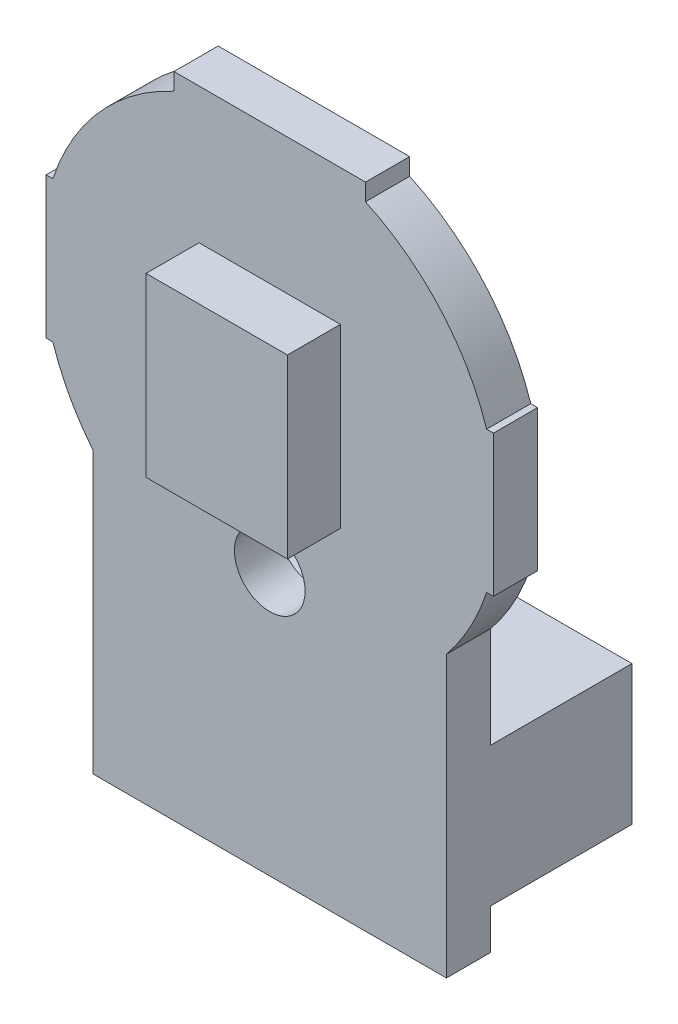
SolidWorks part; units mm, degrees
material "Acetal (Delrin)"
ref_plane "Front" through (0, 0, 0) normal (0, 0, 1) x (1, 0, 0)
ref_plane "Top" through (0, 0, 0) normal (0, 1, 0) x (1, 0, 0)
ref_plane "Right" through (0, 0, 0) normal (1, 0, 0) x (0, 0, -1)
sketch "Sketch1" plane through (0, 0, 0) normal (0, 0, 1) x (1, 0, 0)
  line L0 (-6.35, -9.4973) -> (6.35, -9.4973)
  line L1 (0, -9.4973) -> (0, 0) construction
  line L2 (0, 0) -> (0, 5.7658) construction
  line L3 (-6.35, -9.4973) -> (-6.35, 0.581)
  line L4 (6.35, -9.4973) -> (6.35, 0.581)
  line L7 (-8.0391, 5.7658) -> (0, 5.7658) construction
  line L8 (0, 5.7658) -> (8.0391, 5.7658) construction
  line L10 (3.4417, 13.8199) -> (-3.4417, 13.8199)
  line L11 (0, 1.27) -> (0, 13.8199) construction
  line L12 (3.4417, 13.8199) -> (3.4417, 13.2062)
  line L13 (-3.4417, 13.8199) -> (-3.4417, 13.2062)
  line L14 (-8.0391, 8.3058) -> (-8.0391, 3.2258)
  line L15 (8.0391, 8.3058) -> (8.0391, 3.2258)
  line L16 (-8.0391, 8.3058) -> (-7.7944, 8.3058)
  line L17 (8.0391, 8.3058) -> (7.7944, 8.3058)
  line L18 (8.0391, 3.2258) -> (7.7944, 3.2258)
  line L19 (-8.0391, 3.2258) -> (-7.7944, 3.2258)
  circle A0 centre (0, 0) radius 1.27
  arc A1 (6.35, 0.581) -> (-6.35, 0.581) centre (0, 5.7658) ccw construction
  arc A2 (-7.7944, 3.2258) -> (-6.35, 0.581) centre (0, 5.7658) ccw
  arc A3 (7.7944, 3.2258) -> (6.35, 0.581) centre (0, 5.7658) cw
  arc A4 (3.4417, 13.2062) -> (7.7944, 8.3058) centre (0, 5.7658) cw
  arc A5 (-3.4417, 13.2062) -> (-7.7944, 8.3058) centre (0, 5.7658) ccw
  point P19 (0, 1.27)
  dimension "D1" = 2.54
  dimension "D2" = 8.1978
  dimension "D3" = 12.7
  dimension "D4" = 9.4973
  dimension "D5" = 5.7658
  dimension "D6" = 5.08
  dimension "D7" = 16.0782
  dimension "D8" = 6.8834
  dimension "D9" = 23.3172
extrude "Boss-Extrude1" add sketch "Sketch1" along normal blind 1.5875
sketch "Sketch2" plane through (0, 0, 0) normal (0, 0, -1) x (-1, 0, 0)
  line L0 (6.35, 0.581) -> (6.35, -9.4973) construction
  line L2 (-6.35, -8.0495) -> (-6.35, -3.0457)
  line L3 (-6.35, -3.0457) -> (6.35, -3.0457)
  line L4 (6.35, -8.0495) -> (6.35, -3.0457)
  line L5 (-6.35, -9.4973) -> (-6.35, 0.581) construction
  line L6 (-5.588, -7.2875) -> (5.588, -7.2875)
  line L7 (-5.588, -7.2875) -> (-5.588, -3.8077)
  line L8 (-5.588, -3.8077) -> (5.588, -3.8077)
  line L9 (5.588, -7.2875) -> (5.588, -3.8077)
  line L10 (6.35, 0.581) -> (6.35, -9.4973) construction
  line L11 (6.35, -8.0495) -> (-6.35, -8.0495)
  line L12 (6.35, -9.4973) -> (-6.35, -9.4973) construction
  dimension "D1" = 0.762
  dimension "D2" = 0.762
  dimension "D3" = 0.762
  dimension "D4" = 1.4478
  dimension "D5" = 0.762
  dimension "D6" = 6.4516
  dimension "D7" = 5.0038
extrude "Boss-Extrude2" add sketch "Sketch2" along normal blind 5.08 separate body
sketch "Sketch4" plane through (0, 0, 1.5875) normal (0, 0, 1) x (1, 0, 0)
  line L0 (0, 13.8199) -> (0, 8.9408) construction
  line L1 (-2.54, 8.9408) -> (2.54, 8.9408)
  line L2 (-2.54, 8.9408) -> (-2.54, 2.5908)
  line L3 (-2.54, 2.5908) -> (2.54, 2.5908)
  line L4 (2.54, 8.9408) -> (2.54, 2.5908)
  line L6 (-2.54, 5.7658) -> (0, 5.7658) construction
  line L7 (0, 5.7658) -> (2.54, 5.7658) construction
  line L8 (3.4417, 13.8199) -> (-3.4417, 13.8199) construction
  dimension "D1" = 5.08
  dimension "D2" = 6.35
extrude "Boss-Extrude3" add sketch "Sketch4" along normal blind 1.905 separate body
sketch "Sketch5" plane through (0, 0, 0) normal (0, 0, -1) x (-1, 0, 0)
  line L1 (-5.588, -3.8077) -> (5.588, -3.8077)
  line L2 (-5.588, -3.8077) -> (-5.588, -7.2875)
  line L3 (-5.588, -7.2875) -> (5.588, -7.2875)
  line L4 (5.588, -3.8077) -> (5.588, -7.2875)
extrude "Boss-Extrude4" add sketch "Sketch5" along normal blind 0.508 separate body
sketch "Sketch6" plane through (0, 0, -0.508) normal (0, 0, -1) x (-1, 0, 0)
  line L1 (2.9845, -4.7221) -> (3.3655, -4.7221)
  line L2 (2.9845, -4.7221) -> (2.9845, -5.1031)
  line L3 (2.9845, -5.1031) -> (3.3655, -5.1031)
  line L4 (3.3655, -4.7221) -> (3.3655, -5.1031)
  line L5 (5.588, -5.5476) -> (-5.588, -5.5476) construction
  line L6 (2.9845, -5.9921) -> (3.3655, -5.9921)
  line L7 (2.9845, -5.9921) -> (2.9845, -6.3731)
  line L8 (2.9845, -6.3731) -> (3.3655, -6.3731)
  line L9 (3.3655, -5.9921) -> (3.3655, -6.3731)
  line L10 (5.588, -7.2875) -> (5.588, -3.8077) construction
  line L11 (-5.588, -3.8077) -> (-5.588, -7.2875) construction
  line L13 (5.588, -7.2875) -> (5.588, -3.8077) construction
  dimension "D1" = 0.381
  dimension "D2" = 1.27
  dimension "D3" = 2.2225
extrude "Boss-Extrude5" add sketch "Sketch6" along normal offset from surface (4.064 mm away) 0.508 up to face at (0, -5.5476, -5.08)
pattern_linear "LPattern1" count 5 spacing 1.5875 along (1, 0, 0) of "Boss-Extrude5"
sketch "Sketch7" plane through (0, 0, 0) normal (0, 0, -1) x (-1, 0, 0)
  line L0 (0, 0) -> (0, 11.7602) construction
  line L1 (-0.762, 12.5222) -> (0.762, 12.5222)
  line L2 (-0.762, 12.5222) -> (-0.762, 11.7602)
  line L3 (-0.762, 11.7602) -> (0.762, 11.7602)
  line L4 (0.762, 12.5222) -> (0.762, 11.7602)
  line L5 (-0.254, 11.2522) -> (1.524, 11.2522)
  line L6 (-0.254, 11.2522) -> (-0.254, 10.2362)
  line L7 (-0.254, 10.2362) -> (1.524, 10.2362)
  line L8 (1.524, 11.2522) -> (1.524, 10.2362)
  line L9 (-4.9911, 8.1049) -> (-3.9751, 8.1049)
  line L10 (-4.9911, 8.1049) -> (-4.9911, 6.3269)
  line L11 (-4.9911, 6.3269) -> (-3.9751, 6.3269)
  line L12 (-3.9751, 8.1049) -> (-3.9751, 6.3269)
  line L13 (3.9751, 7.0889) -> (4.9911, 7.0889)
  line L14 (3.9751, 7.0889) -> (3.9751, 5.3109)
  line L15 (3.9751, 5.3109) -> (4.9911, 5.3109)
  line L16 (4.9911, 7.0889) -> (4.9911, 5.3109)
  line L17 (3.0946, 3.8674) -> (6.1426, 3.8674)
  line L18 (3.0946, 3.8674) -> (3.0946, 2.3434)
  line L19 (3.0946, 2.3434) -> (6.1426, 2.3434)
  line L20 (6.1426, 3.8674) -> (6.1426, 2.3434)
  line L21 (-5.0182, 0.6131) -> (-4.3832, 0.6131)
  line L22 (-5.0182, 0.6131) -> (-5.0182, -0.3521)
  line L23 (-5.0182, -0.3521) -> (-4.3832, -0.3521)
  line L24 (-4.3832, 0.6131) -> (-4.3832, -0.3521)
  line L25 (-3.7482, 0.6131) -> (-3.1132, 0.6131)
  line L26 (-3.7482, 0.6131) -> (-3.7482, -0.3521)
  line L27 (-3.7482, -0.3521) -> (-3.1132, -0.3521)
  line L28 (-3.1132, 0.6131) -> (-3.1132, -0.3521)
  line L29 (0, 12.5222) -> (0, 13.8199) construction
  line L33 (6.35, 0.581) -> (6.35, -9.4973) construction
  line L34 (3.556, 0.0023) -> (5.334, 0.0023)
  line L35 (3.556, 0.0023) -> (3.556, -0.7597)
  line L36 (3.556, -0.7597) -> (5.334, -0.7597)
  line L37 (5.334, 0.0023) -> (5.334, -0.7597)
  line L38 (6.35, -3.0457) -> (-6.35, -3.0457) construction
  line L41 (-8.0391, 3.2258) -> (-8.0391, 8.3058) construction
  line L42 (8.0391, 8.3058) -> (8.0391, 3.2258) construction
  line L43 (-3.4417, 13.8199) -> (3.4417, 13.8199) construction
  dimension "D1" = 0.635
  dimension "D2" = 0.635
  dimension "D3" = 0.9652
  dimension "D4" = 3.048
  dimension "D5" = 1.524
  dimension "D6" = 1.016
  dimension "D7" = 1.778
  dimension "D8" = 1.778
  dimension "D9" = 1.016
  dimension "D10" = 1.524
  dimension "D11" = 0.762
  dimension "D12" = 1.016
  dimension "D13" = 1.778
  dimension "D14" = 11.7602
  dimension "D15" = 0.508
  dimension "D16" = 0.508
  dimension "D17" = 3.048
  dimension "D18" = 3.048
  dimension "D19" = 1.016
  dimension "D20" = 9.3726
  dimension "D21" = 2.286
  dimension "D22" = 0.762
  dimension "D23" = 1.778
  dimension "D24" = 1.016
  dimension "D25" = 1.2977
  dimension "D26" = 13.8199
extrude "Boss-Extrude6" add sketch "Sketch7" along normal blind 0.8636 contours L19 L20 L17 L18
extrude "Boss-Extrude7" add sketch "Sketch7<3>" along normal blind 0.508 contours L3 L4 L1 L2 | L36 L37 L34 L35
sketch "Sketch7<3>" plane through (0, 0, 0) normal (0, 0, -1) x (-1, 0, 0) same geometry as "Sketch7"
extrude "Boss-Extrude8" add sketch "Sketch7<4>" along normal blind 0.381 contours L27 L28 L25 L26 | L23 L24 L21 L22
sketch "Sketch7<4>" plane through (0, 0, 0) normal (0, 0, -1) x (-1, 0, 0) same geometry as "Sketch7"
extrude "Boss-Extrude9" add sketch "Sketch7<5>" along normal blind 1.27 contours L15 L16 L13 L14
sketch "Sketch7<5>" plane through (0, 0, 0) normal (0, 0, -1) x (-1, 0, 0) same geometry as "Sketch7"
extrude "Boss-Extrude10" add sketch "Sketch7<6>" along normal blind 0.381 contours L7 L8 L5 L6 | L11 L12 L9 L10
sketch "Sketch7<6>" plane through (0, 0, 0) normal (0, 0, -1) x (-1, 0, 0) same geometry as "Sketch7"
sketch "Sketch10" plane through (0, 0, -5.08) normal (0, 0, -1) x (-1, 0, 0)
  line L0 (6.35, -3.0457) -> (-6.35, -3.0457) construction
  line L1 (-1.2065, -3.0457) -> (1.2065, -3.0457)
  line L2 (-1.2065, -3.0457) -> (-1.2065, -3.8077)
  line L3 (-1.2065, -3.8077) -> (1.2065, -3.8077)
  line L4 (1.2065, -3.0457) -> (1.2065, -3.8077)
  line L5 (5.588, -3.8077) -> (-5.588, -3.8077) construction
  line L6 (0, -3.8077) -> (0, -8.0495) construction
  line L7 (-6.35, -8.0495) -> (6.35, -8.0495) construction
  dimension "D1" = 2.413
extrude "Cut-Extrude2" cut sketch "Sketch10" against normal blind 2.54
combine bodies "Combine2" operation type add bodies to combine 101 118 117 111 110 116 115 108 107 106 103 109
sketch "Sketch11" plane through (0, 0, 0) normal (0, 0, -1) x (-1, 0, 0)
  point P0 (-13.0749, -9.085)
  point P20 (-6.35, -9.4973)
  line B0 (-6.35, -3.0457) -> (6.35, -3.0457)
  line B1 (6.35, -3.0457) -> (6.35, 0.581)
  line B2 (7.7944, 3.2258) -> (8.0391, 3.2258)
  line B3 (8.0391, 3.2258) -> (8.0391, 8.3058)
  line B4 (8.0391, 8.3058) -> (7.7944, 8.3058)
  line B5 (3.4417, 13.2062) -> (3.4417, 13.8199)
  line B6 (3.4417, 13.8199) -> (-3.4417, 13.8199)
  line B7 (-3.4417, 13.8199) -> (-3.4417, 13.2062)
  line B8 (-7.7944, 8.3058) -> (-8.0391, 8.3058)
  line B9 (-8.0391, 8.3058) -> (-8.0391, 3.2258)
  line B10 (-8.0391, 3.2258) -> (-7.7944, 3.2258)
  line B11 (-6.35, 0.581) -> (-6.35, -3.0457)
  line B12 (-5.588, -3.8077) -> (-1.2065, -3.8077)
  line B13 (-1.2065, -3.8077) -> (-1.2065, -3.0457)
  line B14 (-1.2065, -3.0457) -> (-6.35, -3.0457)
  line B15 (-6.35, -3.0457) -> (-6.35, -8.0495)
  line B16 (-6.35, -8.0495) -> (6.35, -8.0495)
  line B17 (6.35, -8.0495) -> (6.35, -3.0457)
  line B18 (6.35, -3.0457) -> (1.2065, -3.0457)
  line B19 (1.2065, -3.0457) -> (1.2065, -3.8077)
  line B20 (1.2065, -3.8077) -> (5.588, -3.8077)
  line B21 (5.588, -3.8077) -> (5.588, -7.2875)
  line B22 (5.588, -7.2875) -> (-5.588, -7.2875)
  line B23 (-5.588, -7.2875) -> (-5.588, -3.8077)
  line B24 (6.35, -8.0495) -> (-6.35, -8.0495)
  line B25 (-6.35, -8.0495) -> (-6.35, -9.4973)
  line B26 (-6.35, -9.4973) -> (6.35, -9.4973)
  line B27 (6.35, -9.4973) -> (6.35, -8.0495)
  circle B28 centre (0, 0) radius 1.27
  arc B29 (6.35, 0.581) -> (7.7944, 3.2258) centre (0, 5.7658) ccw
  arc B30 (7.7944, 8.3058) -> (3.4417, 13.2062) centre (0, 5.7658) ccw
  arc B31 (-3.4417, 13.2062) -> (-7.7944, 8.3058) centre (0, 5.7658) ccw
  arc B32 (-7.7944, 3.2258) -> (-6.35, 0.581) centre (0, 5.7658) ccw
sketch_block_instance "Block1-1"
sketch_block "Block1"
